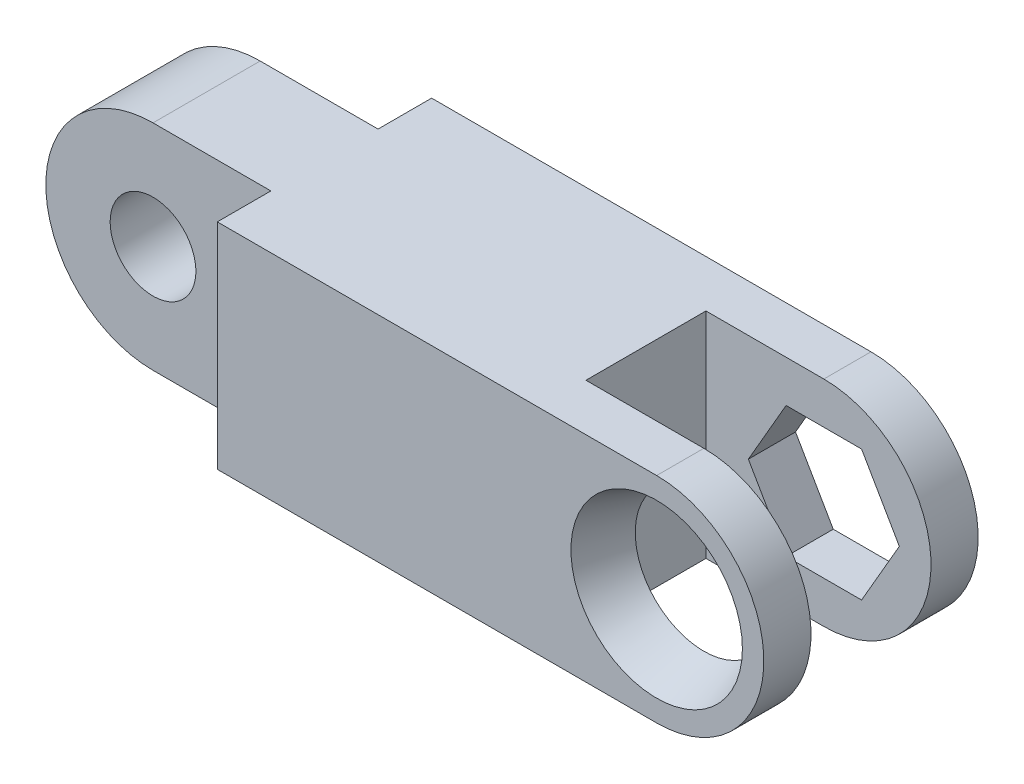
SolidWorks part; units mm, degrees
material "ABS"
ref_plane "前基準面" through (0, 0, 0) normal (0, 0, 1) x (1, 0, 0)
ref_plane "上基準面" through (0, 0, 0) normal (0, 1, 0) x (1, 0, 0)
ref_plane "右基準面" through (0, 0, 0) normal (1, 0, 0) x (0, 0, -1)
sketch "草圖1" plane through (0, 0, 0) normal (0, 0, 1) x (1, 0, 0)
  line L1 (-13, -5) -> (13, -5)
  line L3 (-13, 5) -> (13, 5)
  line L5 (-13, -5) -> (13, 5) construction
  line L6 (-13, 5) -> (13, -5) construction
  arc A0 (13, 5) -> (13, -5) centre (13, 0) cw
  arc A1 (-13, 5) -> (-13, -5) centre (-13, 0) ccw
  point P0 (0, 0)
  dimension "D1" = 10
  dimension "D2" = 26
extrude "填料-伸長1" add sketch "草圖1" along normal blind 10
sketch "草圖2" plane through (0, 0, 10) normal (0, 0, 1) x (1, 0, 0)
  circle A0 centre (-13, 0) radius 2
  circle A1 centre (13, 0) radius 4
  dimension "D1" = 4
  dimension "D2" = 8
sketch "草圖3" plane through (0, 5, 0) normal (0, 1, 0) x (1, 0, 0)
  line L0 (-1020, -5) -> (48980, -5) construction
  line L1 (-13, -10) -> (-13, 0) construction
  line L2 (18, -10) -> (18, 0) construction
  line L3 (7.5, -7.8) -> (18, -7.8)
  line L4 (7.5, -7.8) -> (7.5, -2.2)
  line L5 (7.5, -2.2) -> (18, -2.2)
  line L6 (18, -7.8) -> (18, -2.2)
  line L7 (18, -10) -> (18, 0) construction
  point P5 (-13, -5)
  dimension "D1" = 5.6
  dimension "D2" = 10.5
extrude "除料-伸長2" cut sketch "草圖3" against normal through all
sketch "草圖4" plane through (0, 5, 0) normal (0, 1, 0) x (1, 0, 0)
  line L0 (-13, -5) -> (-27.2142, -5) construction
  line L1 (-13, -10) -> (-13, 0) construction
  line L2 (-13, 0) -> (-18, 0) construction
  line L3 (-18, 0) -> (-7.5, 0)
  line L4 (-18, 0) -> (-18, -2.5)
  line L5 (-18, -2.5) -> (-7.5, -2.5)
  line L6 (-7.5, 0) -> (-7.5, -2.5)
  line L7 (-18, -7.5) -> (-7.5, -7.5)
  line L8 (-7.5, -10) -> (-7.5, -7.5)
  line L9 (-18, -10) -> (-7.5, -10)
  line L10 (-18, -10) -> (-18, -7.5)
  line L11 (-18, 0) -> (-18, -10) construction
  dimension "D1" = 2.5
  dimension "D2" = 10.5
extrude "除料-伸長3" cut sketch "草圖4" against normal through all
extrude "除料-伸長4" cut sketch "草圖2" against normal blind 3 draft 20 contours A1 region at (13, 0, 10)
sketch "草圖5" plane through (0, 0, 0) normal (0, 0, -1) x (-1, 0, 0)
  line L1 (-16.5218, 0) -> (-14.7609, -3.05)
  line L2 (-14.7609, -3.05) -> (-11.2391, -3.05)
  line L3 (-11.2391, -3.05) -> (-9.4782, 0)
  line L4 (-9.4782, 0) -> (-11.2391, 3.05)
  line L5 (-11.2391, 3.05) -> (-14.7609, 3.05)
  line L6 (-14.7609, 3.05) -> (-16.5218, 0)
  circle A0 centre (-13, 0) radius 3.05 construction
  dimension "D1" = 6.1
extrude "除料-伸長5" cut sketch "草圖5" against normal blind 2.5
sketch "草圖6" plane through (0, 0, 0) normal (0, 0, 1) x (1, 0, 0)
  circle A0 centre (-13, 0) radius 2.5
  circle A1 centre (-13, 0) radius 1
  dimension "D1" = 5
  dimension "D2" = 2
extrude "填料-伸長3" [suppressed] add sketch "草圖6" along normal mid plane 1.5 from offset 2.5
fillet "圓角1" [suppressed] radius 0.5
sketch "草圖7" plane through (0, 0, 0) normal (0, 0, 1) x (1, 0, 0)
  line L0 (13, 5) -> (8, 5)
  line L1 (13, 5) -> (-7.5, 5) construction
  line L2 (8, 5) -> (8, -5)
  line L3 (-7.5, -5) -> (13, -5) construction
  line L4 (8, -5) -> (13, -5)
  arc A0 (13, -5) -> (13, 5) centre (13, 0) ccw
extrude "除料-伸長6" [suppressed] cut sketch "草圖7" along normal blind 6 from offset 4.5
sketch "草圖8" plane through (0, 0, 0) normal (0, 0, 1) x (1, 0, 0)
  line L0 (-8.0337, 0.5792) -> (-8, 5)
  line L1 (13, 5) -> (-7.5, 5) construction
  line L2 (-8, 5) -> (-8, -5)
  line L3 (-7.5, -5) -> (13, -5) construction
  line L4 (-8, -5) -> (-13, -5)
  arc A0 (-8.0337, 0.5792) -> (-13, -5) centre (-13, 0) ccw
extrude "除料-伸長7" [suppressed] cut sketch "草圖8" along normal blind 5
pattern_linear "直線複製排列2" [suppressed] count 2 spacing 5 of bodies 111
sketch "草圖9" plane through (0, 0, 0) normal (0, 0, 1) x (1, 0, 0)
  circle A0 centre (-13, 0) radius 2
  dimension "D1" = 4
extrude "除料-伸長8" cut sketch "草圖9" along normal blind 9
